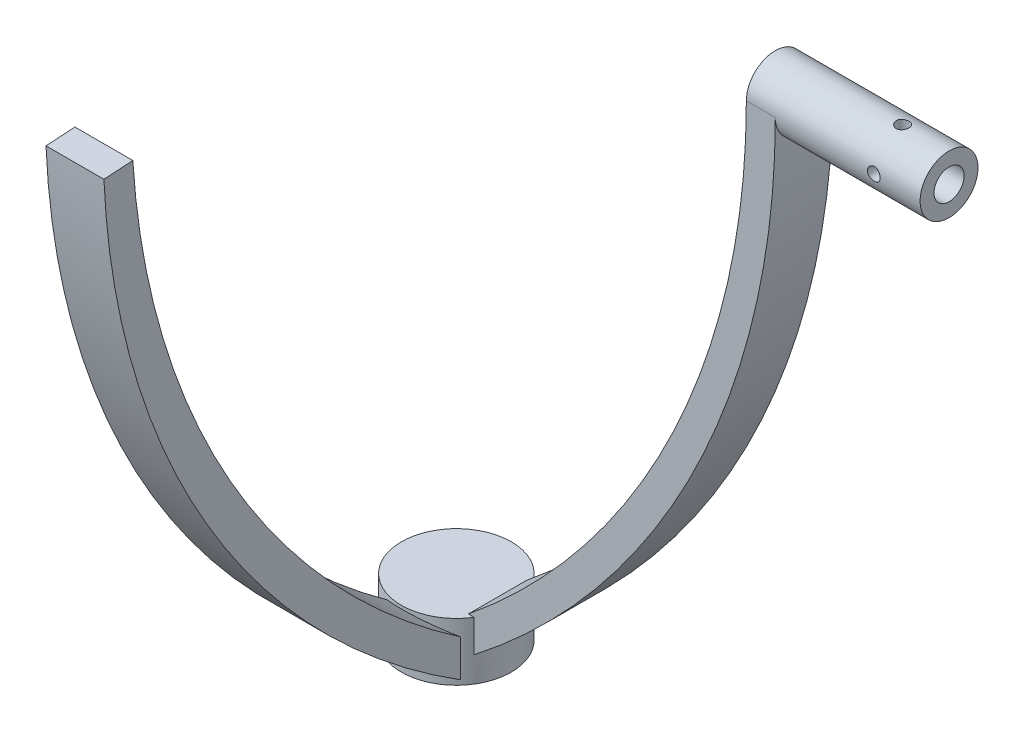
SolidWorks part; units mm, degrees
ref_plane "Front Plane" through (0, 0, 0) normal (0, 0, 1) x (1, 0, 0)
ref_plane "Top Plane" through (0, 0, 0) normal (0, 1, 0) x (1, 0, 0)
ref_plane "Right Plane" through (0, 0, 0) normal (1, 0, 0) x (0, 0, -1)
sketch "Sketch1" plane through (0, 0, 0) normal (1, 0, 0) x (0, 0, -1)
  circle A0 centre (0, 0) radius 5
  dimension "D1" = 10
  dimension "D2" = 0
  dimension "D3" = 0
extrude "Boss-Extrude1" add sketch "Sketch1" along normal blind 25
sketch "Sketch2" plane through (0, 0, 0) normal (-1, 0, 0) x (0, 0, 1)
  circle A0 centre (0, 0) radius 2.6
  dimension "D1" = 5.2
extrude "Cut-Extrude1" cut sketch "Sketch2" against normal blind 25
sketch "Sketch3" plane through (0, 0, 0) normal (0, 1, 0) x (1, 0, 0)
  line L0 (25, -5) -> (25, 5) construction
  circle A0 centre (17, 0) radius 1.1
  dimension "D1" = 2.2
  dimension "D2" = 8
  dimension "D3" = 0
extrude "Cut-Extrude3" cut sketch "Sketch3" against normal blind 25 and the other way blind 25 contours A0
sketch "Sketch4" plane through (0, 0, 0) normal (0, 0, 1) x (1, 0, 0)
  line L0 (25, -5) -> (25, 5) construction
  circle A0 centre (17, 0) radius 1.1
  dimension "D1" = 2.2
  dimension "D2" = 0
  dimension "D3" = 8
extrude "Cut-Extrude4" cut sketch "Sketch4" against normal blind 25 and the other way blind 25
sketch "Sketch5" plane through (0, 0, 0) normal (0, 0, 1) x (1, 0, 0)
  line L0 (-73, -110.7438) -> (-43, -110.7438) construction
  line L1 (0, 0) -> (-5, 0)
  line L3 (-58, -110.7438) -> (-67.164, -110.7438)
  arc A0 (0, 0) -> (-58, -110.7438) centre (-134.7258, 0) cw
  arc A1 (-5, 0) -> (-67.164, -110.7438) centre (-134.7258, 0) cw
  dimension "D4" = 5
  dimension "D1" = 0
  dimension "D2" = 0
  dimension "D3" = 0
  dimension "D5" = 0
  dimension "D6" = 0
extrude "Boss-Extrude2" add sketch "Sketch5" along normal blind 5 and the other way blind 5 separate body contours A1 L3 A0 L1
sketch "Sketch6" plane through (0, 0, 0) normal (-1, 0, 0) x (0, 0, 1)
  circle A0 centre (0, 0) radius 5
extrude "Boss-Extrude3" add sketch "Sketch6" along normal blind 5
ref_plane "Plane1" through (-58, -130.8917, -8.2264) normal (1, 0, 0) x (0, 0.0627, -0.998)
sketch "Sketch7" plane through (-58, -130.8917, -8.2264) normal (1, 0, 0) x (0, 0.0627, -0.998)
  line L0 (-1.9562, 20.3106) -> (-11.9366, 20.9379) construction
  line L2 (-68.071, 131.15) -> (-63.071, 131.15)
  line L3 (-1.9562, 20.6243) -> (-11.9366, 20.9379)
  arc A0 (-63.071, 131.15) -> (-1.9562, 20.6243) centre (67.429, 131.15) ccw
  arc A1 (-11.9366, 20.9379) -> (-68.071, 131.15) centre (63.1408, 128.5787) cw
  point P5 (-6.9464, 20.6243)
  dimension "D5" = 130.5
  dimension "D8" = 5
  dimension "D1" = 0
  dimension "D2" = 0
  dimension "D3" = 0
  dimension "D4" = 0
  dimension "D6" = 0
  dimension "D7" = 5
extrude "Boss-Extrude4" add sketch "Sketch7" along normal blind 5 and the other way blind 5
sketch "Sketch8" plane through (0, -110.7438, 0) normal (0, -1, 0) x (1, 0, 0)
  line L0 (-53, 5) -> (-53, -4.9803) construction
  line L1 (-53, 5) -> (-67.164, 5)
  line L2 (-53, 5) -> (-53, -5)
  line L3 (-53, -5) -> (-67.164, -5)
  line L4 (-67.164, 5) -> (-67.164, -5)
  line L5 (-53, 5) -> (-67.164, -5) construction
  line L6 (-53, -5) -> (-67.164, 5) construction
  line L7 (-53, 5) -> (-58, 5) construction
  circle A0 centre (-60.082, 0) radius 9.5
  point P0 (-60.082, 0)
  line M4 (-63, 5) -> (-67.164, 5)
  line M5 (-67.164, 5) -> (-67.164, -5)
  line M6 (-67.164, -5) -> (-58, -5)
  line M23 (-58, 5) -> (-63, 5)
  dimension "D3" = 19
  dimension "D1" = 0
  dimension "D2" = 0
extrude "Boss-Extrude10" add sketch "Sketch8" against normal blind 10 contours A0 L2 L3 L1 M6 M5 M4 M23 | L2 L3 L4 L1 region at (-69.3133, -110.7438, 0)
